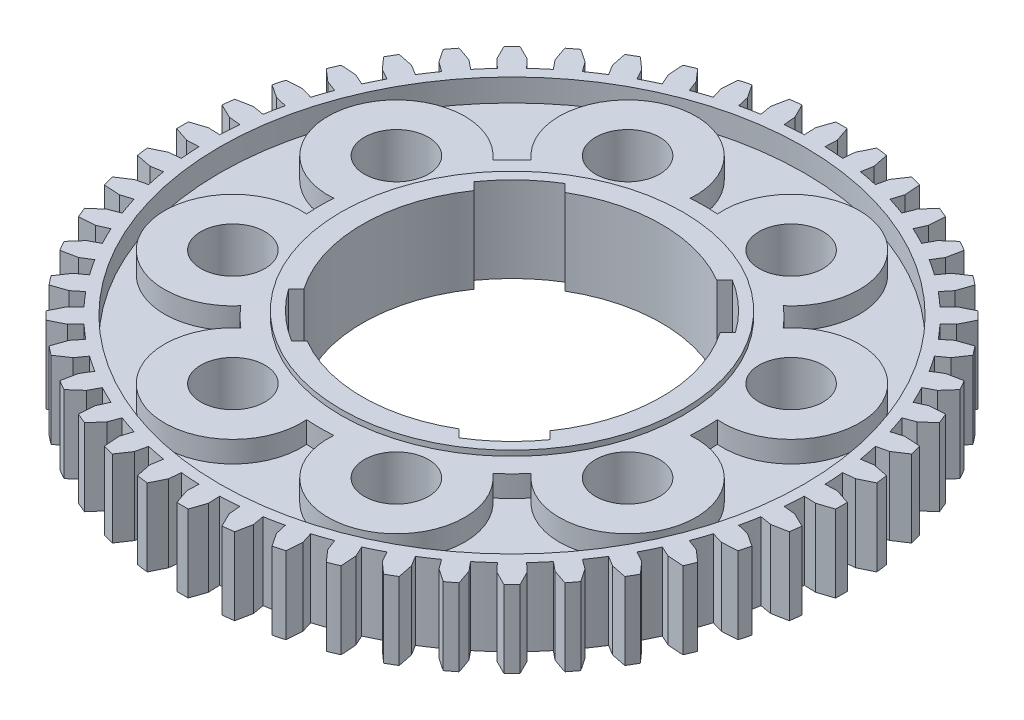
SolidWorks part; units mm, degrees
ref_plane "Plan de face" through (0, 0, 0) normal (0, 0, 1) x (1, 0, 0)
ref_plane "Plan de dessus" through (0, 0, 0) normal (0, 1, 0) x (1, 0, 0)
ref_plane "Plan de droite" through (0, 0, 0) normal (1, 0, 0) x (0, 0, -1)
sketch "Esquisse2" plane through (0, 0, 0) normal (0, 1, 0) x (1, 0, 0)
  line L0 (0, 15) -> (0, 0) construction
  line L1 (0, 0) -> (-15, 0) construction
  line L2 (0, 0) -> (-14, 0) construction
  line L3 (0, 0) -> (0, 14) construction
  line L4 (-7.8424, 12.7866) -> (-7.1138, 12.0579)
  line L5 (0, 0) -> (-15, 15) construction
  line L6 (-14, 0) -> (-18, 0) construction
  line L7 (-12.226, 8.6905) -> (-11.5081, 7.9726)
  line L8 (0, 15) -> (0, 18) construction
  line L9 (0, 0) -> (0, 27.6339) construction
  line L10 (0, 0) -> (-30.1339, 0) construction
  line L11 (0, 0) -> (-18.4776, 7.6537) construction
  line L12 (-27.8401, 11.5317) -> (0, 0) construction
  line L13 (0, 0) -> (-7.6537, 18.4776) construction
  line L14 (-7.6537, 18.4776) -> (-11.5317, 27.8401) construction
  line L15 (-27.8401, 11.5317) -> (-26.0855, 10.805) construction
  line L16 (-4.847, 29.0548) -> (-4.658, 27.9647)
  line L17 (0, 27.6339) -> (0, 30.1339) construction
  line L18 (-4.5538, 30.512) -> (-4.847, 29.0548)
  line L19 (-3.6069, 27.3975) -> (-3.9333, 29.8761) construction
  line L20 (-8.598, 28.1736) -> (-8.2683, 27.1175)
  line L21 (-8.4974, 29.6565) -> (-8.598, 28.1736)
  line L22 (-7.1522, 26.6923) -> (-7.7992, 29.1071) construction
  line L23 (-12.1907, 26.8151) -> (-11.7371, 25.8063)
  line L24 (-12.2957, 28.2937) -> (-12.1907, 26.8151)
  line L25 (0, 0) -> (-21.3079, 21.3079) construction
  line L26 (-10.575, 25.5304) -> (-11.5317, 27.8401) construction
  line L27 (-15.5865, 24.9945) -> (-15.0051, 24.0535)
  line L28 (-11.5317, 27.8401) -> (-10.805, 26.0855) construction
  line L29 (-15.8836, 26.4467) -> (-15.5865, 24.9945)
  line L30 (-13.8169, 23.9317) -> (-15.0669, 26.0967) construction
  line L31 (-18.7156, 22.7462) -> (-18.0163, 21.8892)
  line L32 (-19.1997, 24.1472) -> (-18.7156, 22.7462)
  line L33 (-16.8224, 21.9234) -> (-18.3444, 23.9068) construction
  line L34 (-21.5245, 20.1088) -> (-20.7193, 19.3503)
  line L35 (-22.1873, 21.4346) -> (-21.5245, 20.1088)
  line L36 (-19.5401, 19.5401) -> (-21.3079, 21.3079) construction
  line L37 (-23.965, 17.1272) -> (-23.0677, 16.4803)
  line L38 (-24.7952, 18.3552) -> (-23.965, 17.1272)
  line L39 (-21.9234, 16.8224) -> (-23.9068, 18.3444) construction
  line L40 (-25.9956, 13.8526) -> (-25.0215, 13.3284)
  line L41 (-26.9789, 14.9617) -> (-25.9956, 13.8526)
  line L42 (-23.9317, 13.8169) -> (-26.0967, 15.0669) construction
  line L43 (-27.5813, 10.341) -> (-26.5472, 9.9484)
  line L44 (-28.701, 11.3123) -> (-27.5813, 10.341)
  line L45 (-25.5304, 10.575) -> (-27.8401, 11.5317) construction
  line L46 (-28.6951, 6.6525) -> (-27.6186, 6.3982)
  line L47 (-29.932, 7.4693) -> (-28.6951, 6.6525)
  line L48 (-26.6923, 7.1522) -> (-29.1071, 7.7992) construction
  line L49 (-29.318, 2.8501) -> (-28.2174, 2.7385)
  line L50 (-30.6509, 3.4985) -> (-29.318, 2.8501)
  line L51 (-27.3975, 3.6069) -> (-29.8761, 3.9333) construction
  line L52 (-1.0131, 29.4389) -> (-1.0715, 30.8691) construction
  line L53 (-1.0131, -29.4389) -> (-1.0715, -30.8691) construction
  line L54 (-0.5322, 30.8453) -> (-1.0131, 29.4389)
  line L55 (-1.0131, 29.4389) -> (-0.968, 28.3335)
  line L56 (-27.3975, -3.6069) -> (-29.8761, -3.9333) construction
  line L57 (-27.6339, 0) -> (-30.1339, 0) construction
  line L58 (-3.4985, 30.6509) -> (-2.8381, 29.3193)
  line L59 (-2.8381, 29.3193) -> (-2.7385, 28.2174)
  line L60 (-7.4693, 29.932) -> (-6.6407, 28.698)
  line L61 (-6.6407, 28.698) -> (-6.3982, 27.6186)
  line L62 (-10.341, 27.5813) -> (-9.9484, 26.5472)
  line L63 (-11.3123, 28.701) -> (-10.341, 27.5813)
  line L64 (-14.9617, 26.9789) -> (-13.8526, 25.9956)
  line L65 (-13.8526, 25.9956) -> (-13.3284, 25.0215)
  line L66 (-18.3552, 24.7952) -> (-17.1272, 23.965)
  line L67 (-17.1272, 23.965) -> (-16.4803, 23.0677)
  line L68 (-30.512, 4.5538) -> (-29.0566, 4.8351)
  line L69 (-29.0566, 4.8351) -> (-27.9647, 4.658)
  line L70 (-29.6565, 8.4974) -> (-28.1769, 8.5864)
  line L71 (-28.1769, 8.5864) -> (-27.1175, 8.2683)
  line L72 (-28.2937, 12.2957) -> (-26.8151, 12.1907)
  line L73 (-26.8151, 12.1907) -> (-25.8063, 11.7371)
  line L74 (-26.4467, 15.8836) -> (-24.9945, 15.5865)
  line L75 (-24.9945, 15.5865) -> (-24.0535, 15.0051)
  line L76 (-24.1472, 19.1997) -> (-22.7462, 18.7156)
  line L77 (-22.7462, 18.7156) -> (-21.8892, 18.0163)
  line L78 (-21.4346, 22.1873) -> (-20.1088, 21.5245)
  line L79 (-20.1088, 21.5245) -> (-19.3503, 20.7193)
  line L80 (-30.8451, 0.5443) -> (-29.4389, 1.0131)
  line L81 (-29.4389, 1.0131) -> (-28.3335, 0.968)
  line L82 (-26.6923, -7.1522) -> (-29.1071, -7.7992) construction
  line L83 (-25.5304, -10.575) -> (-27.8401, -11.5317) construction
  line L84 (-23.9317, -13.8169) -> (-26.0967, -15.0669) construction
  line L85 (-21.9234, -16.8224) -> (-23.9068, -18.3444) construction
  line L86 (-19.5401, -19.5401) -> (-21.3079, -21.3079) construction
  line L87 (-16.8224, -21.9234) -> (-18.3444, -23.9068) construction
  line L88 (-13.8169, -23.9317) -> (-15.0669, -26.0967) construction
  line L89 (-11.5317, -27.8401) -> (-10.805, -26.0855) construction
  line L90 (-10.575, -25.5304) -> (-11.5317, -27.8401) construction
  line L91 (0, 0) -> (-21.3079, -21.3079) construction
  line L92 (-7.1522, -26.6923) -> (-7.7992, -29.1071) construction
  line L93 (-3.6069, -27.3975) -> (-3.9333, -29.8761) construction
  line L94 (0, -27.6339) -> (0, -30.1339) construction
  line L95 (-27.8401, -11.5317) -> (-26.0855, -10.805) construction
  line L96 (-7.6537, -18.4776) -> (-11.5317, -27.8401) construction
  line L97 (0, 0) -> (-7.6537, -18.4776) construction
  line L98 (-27.8401, -11.5317) -> (0, 0) construction
  line L99 (0, 0) -> (-18.4776, -7.6537) construction
  line L100 (0, 0) -> (0, -27.6339) construction
  line L101 (0, -15) -> (0, -18) construction
  line L102 (0, 0) -> (-15, -15) construction
  line L103 (0, 0) -> (0, -14) construction
  line L104 (0, -15) -> (0, 0) construction
  line L105 (-29.4389, -1.0131) -> (-28.3335, -0.968)
  line L106 (-30.8451, -0.5443) -> (-29.4389, -1.0131)
  line L107 (-20.1088, -21.5245) -> (-19.3503, -20.7193)
  line L108 (-21.4346, -22.1873) -> (-20.1088, -21.5245)
  line L109 (-22.7462, -18.7156) -> (-21.8892, -18.0163)
  line L110 (-24.1472, -19.1997) -> (-22.7462, -18.7156)
  line L111 (-24.9945, -15.5865) -> (-24.0535, -15.0051)
  line L112 (-26.4467, -15.8836) -> (-24.9945, -15.5865)
  line L113 (-26.8151, -12.1907) -> (-25.8063, -11.7371)
  line L114 (-28.2937, -12.2957) -> (-26.8151, -12.1907)
  line L115 (-28.1769, -8.5864) -> (-27.1175, -8.2683)
  line L116 (-29.6565, -8.4974) -> (-28.1769, -8.5864)
  line L117 (-29.0566, -4.8351) -> (-27.9647, -4.658)
  line L118 (-30.512, -4.5538) -> (-29.0566, -4.8351)
  line L119 (-17.1272, -23.965) -> (-16.4803, -23.0677)
  line L120 (-18.3552, -24.7952) -> (-17.1272, -23.965)
  line L121 (-13.8526, -25.9956) -> (-13.3284, -25.0215)
  line L122 (-14.9617, -26.9789) -> (-13.8526, -25.9956)
  line L123 (-11.3123, -28.701) -> (-10.341, -27.5813)
  line L124 (-10.341, -27.5813) -> (-9.9484, -26.5472)
  line L125 (-6.6407, -28.698) -> (-6.3982, -27.6186)
  line L126 (-7.4693, -29.932) -> (-6.6407, -28.698)
  line L127 (-2.8381, -29.3193) -> (-2.7385, -28.2174)
  line L128 (-3.4985, -30.6509) -> (-2.8381, -29.3193)
  line L129 (-1.0131, -29.4389) -> (-0.968, -28.3335)
  line L130 (-0.5322, -30.8453) -> (-1.0131, -29.4389)
  line L131 (-30.6509, -3.4985) -> (-29.318, -2.8501)
  line L132 (-29.318, -2.8501) -> (-28.2174, -2.7385)
  line L133 (-29.932, -7.4693) -> (-28.6951, -6.6525)
  line L134 (-28.6951, -6.6525) -> (-27.6186, -6.3982)
  line L135 (-28.701, -11.3123) -> (-27.5813, -10.341)
  line L136 (-27.5813, -10.341) -> (-26.5472, -9.9484)
  line L137 (-26.9789, -14.9617) -> (-25.9956, -13.8526)
  line L138 (-25.9956, -13.8526) -> (-25.0215, -13.3284)
  line L139 (-24.7952, -18.3552) -> (-23.965, -17.1272)
  line L140 (-23.965, -17.1272) -> (-23.0677, -16.4803)
  line L141 (-22.1873, -21.4346) -> (-21.5245, -20.1088)
  line L142 (-21.5245, -20.1088) -> (-20.7193, -19.3503)
  line L143 (-19.1997, -24.1472) -> (-18.7156, -22.7462)
  line L144 (-18.7156, -22.7462) -> (-18.0163, -21.8892)
  line L145 (-15.8836, -26.4467) -> (-15.5865, -24.9945)
  line L146 (-15.5865, -24.9945) -> (-15.0051, -24.0535)
  line L147 (-12.2957, -28.2937) -> (-12.1907, -26.8151)
  line L148 (-12.1907, -26.8151) -> (-11.7371, -25.8063)
  line L149 (-8.4974, -29.6565) -> (-8.598, -28.1736)
  line L150 (-8.598, -28.1736) -> (-8.2683, -27.1175)
  line L151 (-4.5538, -30.512) -> (-4.847, -29.0548)
  line L152 (-4.847, -29.0548) -> (-4.658, -27.9647)
  line L153 (-12.226, -8.6905) -> (-11.5081, -7.9726)
  line L154 (-7.8424, -12.7866) -> (-7.1138, -12.0579)
  line L155 (0, 0) -> (15, -15) construction
  line L156 (0, 0) -> (18.4776, -7.6537) construction
  line L157 (27.8401, -11.5317) -> (0, 0) construction
  line L158 (0, 0) -> (7.6537, -18.4776) construction
  line L159 (7.6537, -18.4776) -> (11.5317, -27.8401) construction
  line L160 (27.8401, -11.5317) -> (26.0855, -10.805) construction
  line L161 (3.6069, -27.3975) -> (3.9333, -29.8761) construction
  line L162 (7.1522, -26.6923) -> (7.7992, -29.1071) construction
  line L163 (0, 0) -> (21.3079, -21.3079) construction
  line L164 (10.575, -25.5304) -> (11.5317, -27.8401) construction
  line L165 (11.5317, -27.8401) -> (10.805, -26.0855) construction
  line L166 (13.8169, -23.9317) -> (15.0669, -26.0967) construction
  line L167 (16.8224, -21.9234) -> (18.3444, -23.9068) construction
  line L168 (19.5401, -19.5401) -> (21.3079, -21.3079) construction
  line L169 (21.9234, -16.8224) -> (23.9068, -18.3444) construction
  line L170 (23.9317, -13.8169) -> (26.0967, -15.0669) construction
  line L171 (25.5304, -10.575) -> (27.8401, -11.5317) construction
  line L172 (26.6923, -7.1522) -> (29.1071, -7.7992) construction
  line L173 (27.6339, 0) -> (30.1339, 0) construction
  line L174 (27.3975, -3.6069) -> (29.8761, -3.9333) construction
  line L175 (1.0131, -29.4389) -> (1.0715, -30.8691) construction
  line L176 (1.0131, 29.4389) -> (1.0715, 30.8691) construction
  line L177 (27.3975, 3.6069) -> (29.8761, 3.9333) construction
  line L178 (26.6923, 7.1522) -> (29.1071, 7.7992) construction
  line L179 (25.5304, 10.575) -> (27.8401, 11.5317) construction
  line L180 (23.9317, 13.8169) -> (26.0967, 15.0669) construction
  line L181 (21.9234, 16.8224) -> (23.9068, 18.3444) construction
  line L182 (19.5401, 19.5401) -> (21.3079, 21.3079) construction
  line L183 (16.8224, 21.9234) -> (18.3444, 23.9068) construction
  line L184 (13.8169, 23.9317) -> (15.0669, 26.0967) construction
  line L185 (11.5317, 27.8401) -> (10.805, 26.0855) construction
  line L186 (10.575, 25.5304) -> (11.5317, 27.8401) construction
  line L187 (0, 0) -> (21.3079, 21.3079) construction
  line L188 (7.1522, 26.6923) -> (7.7992, 29.1071) construction
  line L189 (3.6069, 27.3975) -> (3.9333, 29.8761) construction
  line L190 (27.8401, 11.5317) -> (26.0855, 10.805) construction
  line L191 (7.6537, 18.4776) -> (11.5317, 27.8401) construction
  line L192 (0, 0) -> (7.6537, 18.4776) construction
  line L193 (27.8401, 11.5317) -> (0, 0) construction
  line L194 (0, 0) -> (18.4776, 7.6537) construction
  line L195 (0, 0) -> (30.1339, 0) construction
  line L196 (14, 0) -> (18, 0) construction
  line L197 (0, 0) -> (15, 15) construction
  line L198 (0, 0) -> (14, 0) construction
  line L199 (0, 0) -> (15, 0) construction
  line L200 (7.8424, -12.7866) -> (7.1138, -12.0579)
  line L201 (12.226, -8.6905) -> (11.5081, -7.9726)
  line L202 (4.847, -29.0548) -> (4.658, -27.9647)
  line L203 (4.5538, -30.512) -> (4.847, -29.0548)
  line L204 (8.598, -28.1736) -> (8.2683, -27.1175)
  line L205 (8.4974, -29.6565) -> (8.598, -28.1736)
  line L206 (12.1907, -26.8151) -> (11.7371, -25.8063)
  line L207 (12.2957, -28.2937) -> (12.1907, -26.8151)
  line L208 (15.5865, -24.9945) -> (15.0051, -24.0535)
  line L209 (15.8836, -26.4467) -> (15.5865, -24.9945)
  line L210 (18.7156, -22.7462) -> (18.0163, -21.8892)
  line L211 (19.1997, -24.1472) -> (18.7156, -22.7462)
  line L212 (21.5245, -20.1088) -> (20.7193, -19.3503)
  line L213 (22.1873, -21.4346) -> (21.5245, -20.1088)
  line L214 (23.965, -17.1272) -> (23.0677, -16.4803)
  line L215 (24.7952, -18.3552) -> (23.965, -17.1272)
  line L216 (25.9956, -13.8526) -> (25.0215, -13.3284)
  line L217 (26.9789, -14.9617) -> (25.9956, -13.8526)
  line L218 (27.5813, -10.341) -> (26.5472, -9.9484)
  line L219 (28.701, -11.3123) -> (27.5813, -10.341)
  line L220 (28.6951, -6.6525) -> (27.6186, -6.3982)
  line L221 (29.932, -7.4693) -> (28.6951, -6.6525)
  line L222 (29.318, -2.8501) -> (28.2174, -2.7385)
  line L223 (30.6509, -3.4985) -> (29.318, -2.8501)
  line L224 (0.5322, -30.8453) -> (1.0131, -29.4389)
  line L225 (1.0131, -29.4389) -> (0.968, -28.3335)
  line L226 (3.4985, -30.6509) -> (2.8381, -29.3193)
  line L227 (2.8381, -29.3193) -> (2.7385, -28.2174)
  line L228 (7.4693, -29.932) -> (6.6407, -28.698)
  line L229 (6.6407, -28.698) -> (6.3982, -27.6186)
  line L230 (10.341, -27.5813) -> (9.9484, -26.5472)
  line L231 (11.3123, -28.701) -> (10.341, -27.5813)
  line L232 (14.9617, -26.9789) -> (13.8526, -25.9956)
  line L233 (13.8526, -25.9956) -> (13.3284, -25.0215)
  line L234 (18.3552, -24.7952) -> (17.1272, -23.965)
  line L235 (17.1272, -23.965) -> (16.4803, -23.0677)
  line L236 (30.512, -4.5538) -> (29.0566, -4.8351)
  line L237 (29.0566, -4.8351) -> (27.9647, -4.658)
  line L238 (29.6565, -8.4974) -> (28.1769, -8.5864)
  line L239 (28.1769, -8.5864) -> (27.1175, -8.2683)
  line L240 (28.2937, -12.2957) -> (26.8151, -12.1907)
  line L241 (26.8151, -12.1907) -> (25.8063, -11.7371)
  line L242 (26.4467, -15.8836) -> (24.9945, -15.5865)
  line L243 (24.9945, -15.5865) -> (24.0535, -15.0051)
  line L244 (24.1472, -19.1997) -> (22.7462, -18.7156)
  line L245 (22.7462, -18.7156) -> (21.8892, -18.0163)
  line L246 (21.4346, -22.1873) -> (20.1088, -21.5245)
  line L247 (20.1088, -21.5245) -> (19.3503, -20.7193)
  line L248 (30.8451, -0.5443) -> (29.4389, -1.0131)
  line L249 (29.4389, -1.0131) -> (28.3335, -0.968)
  line L250 (29.4389, 1.0131) -> (28.3335, 0.968)
  line L251 (30.8451, 0.5443) -> (29.4389, 1.0131)
  line L252 (20.1088, 21.5245) -> (19.3503, 20.7193)
  line L253 (21.4346, 22.1873) -> (20.1088, 21.5245)
  line L254 (22.7462, 18.7156) -> (21.8892, 18.0163)
  line L255 (24.1472, 19.1997) -> (22.7462, 18.7156)
  line L256 (24.9945, 15.5865) -> (24.0535, 15.0051)
  line L257 (26.4467, 15.8836) -> (24.9945, 15.5865)
  line L258 (26.8151, 12.1907) -> (25.8063, 11.7371)
  line L259 (28.2937, 12.2957) -> (26.8151, 12.1907)
  line L260 (28.1769, 8.5864) -> (27.1175, 8.2683)
  line L261 (29.6565, 8.4974) -> (28.1769, 8.5864)
  line L262 (29.0566, 4.8351) -> (27.9647, 4.658)
  line L263 (30.512, 4.5538) -> (29.0566, 4.8351)
  line L264 (17.1272, 23.965) -> (16.4803, 23.0677)
  line L265 (18.3552, 24.7952) -> (17.1272, 23.965)
  line L266 (13.8526, 25.9956) -> (13.3284, 25.0215)
  line L267 (14.9617, 26.9789) -> (13.8526, 25.9956)
  line L268 (11.3123, 28.701) -> (10.341, 27.5813)
  line L269 (10.341, 27.5813) -> (9.9484, 26.5472)
  line L270 (6.6407, 28.698) -> (6.3982, 27.6186)
  line L271 (7.4693, 29.932) -> (6.6407, 28.698)
  line L272 (2.8381, 29.3193) -> (2.7385, 28.2174)
  line L273 (3.4985, 30.6509) -> (2.8381, 29.3193)
  line L274 (1.0131, 29.4389) -> (0.968, 28.3335)
  line L275 (0.5322, 30.8453) -> (1.0131, 29.4389)
  line L276 (30.6509, 3.4985) -> (29.318, 2.8501)
  line L277 (29.318, 2.8501) -> (28.2174, 2.7385)
  line L278 (29.932, 7.4693) -> (28.6951, 6.6525)
  line L279 (28.6951, 6.6525) -> (27.6186, 6.3982)
  line L280 (28.701, 11.3123) -> (27.5813, 10.341)
  line L281 (27.5813, 10.341) -> (26.5472, 9.9484)
  line L282 (26.9789, 14.9617) -> (25.9956, 13.8526)
  line L283 (25.9956, 13.8526) -> (25.0215, 13.3284)
  line L284 (24.7952, 18.3552) -> (23.965, 17.1272)
  line L285 (23.965, 17.1272) -> (23.0677, 16.4803)
  line L286 (22.1873, 21.4346) -> (21.5245, 20.1088)
  line L287 (21.5245, 20.1088) -> (20.7193, 19.3503)
  line L288 (19.1997, 24.1472) -> (18.7156, 22.7462)
  line L289 (18.7156, 22.7462) -> (18.0163, 21.8892)
  line L290 (15.8836, 26.4467) -> (15.5865, 24.9945)
  line L291 (15.5865, 24.9945) -> (15.0051, 24.0535)
  line L292 (12.2957, 28.2937) -> (12.1907, 26.8151)
  line L293 (12.1907, 26.8151) -> (11.7371, 25.8063)
  line L294 (8.4974, 29.6565) -> (8.598, 28.1736)
  line L295 (8.598, 28.1736) -> (8.2683, 27.1175)
  line L296 (4.5538, 30.512) -> (4.847, 29.0548)
  line L297 (4.847, 29.0548) -> (4.658, 27.9647)
  line L298 (12.226, 8.6905) -> (11.5081, 7.9726)
  line L299 (7.8424, 12.7866) -> (7.1138, 12.0579)
  arc A0 (-7.8424, 12.7866) -> (-12.226, 8.6905) centre (0, 0) ccw
  arc A1 (7.1138, 12.0579) -> (-7.1138, 12.0579) centre (0, 0) ccw
  arc A2 (-11.5081, 7.9726) -> (-11.5081, -7.9726) centre (0, 0) ccw
  arc A3 (-17.9548, 1.2751) -> (-17.9548, -1.2751) centre (0, 0) ccw
  circle A4 centre (-7.6537, 18.4776) radius 3
  arc A5 (-1.2751, 17.9548) -> (-11.7943, 13.5976) centre (-7.6537, 18.4776) ccw
  arc A6 (-17.9548, 1.2751) -> (-13.5976, 11.7943) centre (-18.4776, 7.6537) cw
  circle A7 centre (-18.4776, 7.6537) radius 3
  arc A8 (-11.7943, 13.5976) -> (-13.5976, 11.7943) centre (0, 0) ccw
  arc A9 (1.2751, 17.9548) -> (-1.2751, 17.9548) centre (0, 0) ccw
  circle A10 centre (0, 0) radius 27.35
  circle A11 centre (0, 0) radius 16
  arc A12 (-0.968, 28.3335) -> (-2.7385, 28.2174) centre (0, 0) ccw
  arc A14 (0.5322, 30.8453) -> (-0.5322, 30.8453) centre (0, 0) ccw
  arc A15 (-30.8451, 0.5443) -> (-30.8451, -0.5443) centre (0, 0) ccw
  arc A16 (-26.5472, 9.9484) -> (-27.1175, 8.2683) centre (0, 0) ccw
  arc A19 (-30.512, 4.5538) -> (-30.6509, 3.4985) centre (0, 0) ccw
  arc A20 (-11.7371, 25.8063) -> (-13.3284, 25.0215) centre (0, 0) ccw
  arc A21 (-29.6565, 8.4974) -> (-29.932, 7.4693) centre (0, 0) ccw
  arc A22 (-28.2937, 12.2957) -> (-28.701, 11.3123) centre (0, 0) ccw
  arc A23 (-26.4467, 15.8836) -> (-26.9789, 14.9617) centre (0, 0) ccw
  arc A24 (-24.1472, 19.1997) -> (-24.7952, 18.3552) centre (0, 0) ccw
  arc A25 (-21.4346, 22.1873) -> (-22.1873, 21.4346) centre (0, 0) ccw
  arc A27 (-18.3552, 24.7952) -> (-19.1997, 24.1472) centre (0, 0) ccw
  arc A28 (-14.9617, 26.9789) -> (-15.8836, 26.4467) centre (0, 0) ccw
  arc A29 (-11.3123, 28.701) -> (-12.2957, 28.2937) centre (0, 0) ccw
  arc A32 (-7.4693, 29.932) -> (-8.4974, 29.6565) centre (0, 0) ccw
  arc A33 (-3.4985, 30.6509) -> (-4.5538, 30.512) centre (0, 0) ccw
  arc A34 (-4.658, 27.9647) -> (-6.3982, 27.6186) centre (0, 0) ccw
  arc A35 (-8.2683, 27.1175) -> (-9.9484, 26.5472) centre (0, 0) ccw
  arc A44 (-11.7371, 25.8063) -> (-13.3284, 25.0215) centre (0, 0) ccw
  arc A59 (-15.0051, 24.0535) -> (-16.4803, 23.0677) centre (0, 0) ccw
  arc A60 (-18.0163, 21.8892) -> (-19.3503, 20.7193) centre (0, 0) ccw
  arc A61 (-20.7193, 19.3503) -> (-21.8892, 18.0163) centre (0, 0) ccw
  arc A62 (-23.0677, 16.4803) -> (-24.0535, 15.0051) centre (0, 0) ccw
  arc A63 (-25.0215, 13.3284) -> (-25.8063, 11.7371) centre (0, 0) ccw
  arc A64 (-26.5472, 9.9484) -> (-27.1175, 8.2683) centre (0, 0) ccw
  arc A65 (-27.6186, 6.3982) -> (-27.9647, 4.658) centre (0, 0) ccw
  arc A66 (-28.2174, 2.7385) -> (-28.3335, 0.968) centre (0, 0) ccw
  arc A67 (-0.968, 28.3335) -> (-2.7385, 28.2174) centre (0, 0) ccw
  arc A68 (-0.968, 28.3335) -> (-2.7385, 28.2174) centre (0, 0) ccw
  arc A69 (-28.2174, 2.7385) -> (-28.3335, 0.968) centre (0, 0) ccw
  arc A70 (-27.6186, 6.3982) -> (-27.9647, 4.658) centre (0, 0) ccw
  arc A71 (-27.6186, 6.3982) -> (-28.3335, 0.968) centre (0, 0) ccw
  arc A72 (-26.5472, 9.9484) -> (-27.1175, 8.2683) centre (0, 0) ccw
  arc A73 (-25.0215, 13.3284) -> (-25.8063, 11.7371) centre (0, 0) ccw
  arc A74 (-25.0215, 13.3284) -> (-25.8063, 11.7371) centre (0, 0) ccw
  arc A75 (-23.0677, 16.4803) -> (-24.0535, 15.0051) centre (0, 0) ccw
  arc A76 (-23.0677, 16.4803) -> (-24.0535, 15.0051) centre (0, 0) ccw
  arc A77 (-20.7193, 19.3503) -> (-21.8892, 18.0163) centre (0, 0) ccw
  arc A78 (-20.7193, 19.3503) -> (-21.8892, 18.0163) centre (0, 0) ccw
  arc A79 (-18.0163, 21.8892) -> (-19.3503, 20.7193) centre (0, 0) ccw
  arc A80 (-18.0163, 21.8892) -> (-19.3503, 20.7193) centre (0, 0) ccw
  arc A81 (-15.0051, 24.0535) -> (-16.4803, 23.0677) centre (0, 0) ccw
  arc A82 (-15.0051, 24.0535) -> (-16.4803, 23.0677) centre (0, 0) ccw
  arc A83 (-11.7371, 25.8063) -> (-13.3284, 25.0215) centre (0, 0) ccw
  arc A84 (-8.2683, 27.1175) -> (-9.9484, 26.5472) centre (0, 0) ccw
  arc A85 (-8.2683, 27.1175) -> (-9.9484, 26.5472) centre (0, 0) ccw
  arc A86 (-4.658, 27.9647) -> (-6.3982, 27.6186) centre (0, 0) ccw
  arc A87 (-4.658, 27.9647) -> (-6.3982, 27.6186) centre (0, 0) ccw
  arc A88 (-4.658, -27.9647) -> (-6.3982, -27.6186) centre (0, 0) cw
  arc A89 (-4.658, -27.9647) -> (-6.3982, -27.6186) centre (0, 0) cw
  arc A90 (-8.2683, -27.1175) -> (-9.9484, -26.5472) centre (0, 0) cw
  arc A91 (-8.2683, -27.1175) -> (-9.9484, -26.5472) centre (0, 0) cw
  arc A92 (-11.7371, -25.8063) -> (-13.3284, -25.0215) centre (0, 0) cw
  arc A93 (-15.0051, -24.0535) -> (-16.4803, -23.0677) centre (0, 0) cw
  arc A94 (-15.0051, -24.0535) -> (-16.4803, -23.0677) centre (0, 0) cw
  arc A95 (-18.0163, -21.8892) -> (-19.3503, -20.7193) centre (0, 0) cw
  arc A96 (-18.0163, -21.8892) -> (-19.3503, -20.7193) centre (0, 0) cw
  arc A97 (-20.7193, -19.3503) -> (-21.8892, -18.0163) centre (0, 0) cw
  arc A98 (-20.7193, -19.3503) -> (-21.8892, -18.0163) centre (0, 0) cw
  arc A99 (-23.0677, -16.4803) -> (-24.0535, -15.0051) centre (0, 0) cw
  arc A100 (-23.0677, -16.4803) -> (-24.0535, -15.0051) centre (0, 0) cw
  arc A101 (-25.0215, -13.3284) -> (-25.8063, -11.7371) centre (0, 0) cw
  arc A102 (-25.0215, -13.3284) -> (-25.8063, -11.7371) centre (0, 0) cw
  arc A103 (-26.5472, -9.9484) -> (-27.1175, -8.2683) centre (0, 0) cw
  arc A104 (-27.6186, -6.3982) -> (-28.3335, -0.968) centre (0, 0) cw
  arc A105 (-27.6186, -6.3982) -> (-27.9647, -4.658) centre (0, 0) cw
  arc A106 (-28.2174, -2.7385) -> (-28.3335, -0.968) centre (0, 0) cw
  arc A107 (-0.968, -28.3335) -> (-2.7385, -28.2174) centre (0, 0) cw
  arc A108 (-0.968, -28.3335) -> (-2.7385, -28.2174) centre (0, 0) cw
  arc A109 (-28.2174, -2.7385) -> (-28.3335, -0.968) centre (0, 0) cw
  arc A110 (-27.6186, -6.3982) -> (-27.9647, -4.658) centre (0, 0) cw
  arc A111 (-26.5472, -9.9484) -> (-27.1175, -8.2683) centre (0, 0) cw
  arc A112 (-25.0215, -13.3284) -> (-25.8063, -11.7371) centre (0, 0) cw
  arc A113 (-23.0677, -16.4803) -> (-24.0535, -15.0051) centre (0, 0) cw
  arc A114 (-20.7193, -19.3503) -> (-21.8892, -18.0163) centre (0, 0) cw
  arc A115 (-18.0163, -21.8892) -> (-19.3503, -20.7193) centre (0, 0) cw
  arc A116 (-15.0051, -24.0535) -> (-16.4803, -23.0677) centre (0, 0) cw
  arc A117 (-11.7371, -25.8063) -> (-13.3284, -25.0215) centre (0, 0) cw
  arc A118 (-8.2683, -27.1175) -> (-9.9484, -26.5472) centre (0, 0) cw
  arc A119 (-4.658, -27.9647) -> (-6.3982, -27.6186) centre (0, 0) cw
  arc A120 (-3.4985, -30.6509) -> (-4.5538, -30.512) centre (0, 0) cw
  arc A121 (-7.4693, -29.932) -> (-8.4974, -29.6565) centre (0, 0) cw
  arc A122 (-11.3123, -28.701) -> (-12.2957, -28.2937) centre (0, 0) cw
  arc A123 (-14.9617, -26.9789) -> (-15.8836, -26.4467) centre (0, 0) cw
  arc A124 (-18.3552, -24.7952) -> (-19.1997, -24.1472) centre (0, 0) cw
  arc A125 (-21.4346, -22.1873) -> (-22.1873, -21.4346) centre (0, 0) cw
  arc A126 (-24.1472, -19.1997) -> (-24.7952, -18.3552) centre (0, 0) cw
  arc A127 (-26.4467, -15.8836) -> (-26.9789, -14.9617) centre (0, 0) cw
  arc A128 (-28.2937, -12.2957) -> (-28.701, -11.3123) centre (0, 0) cw
  arc A129 (-29.6565, -8.4974) -> (-29.932, -7.4693) centre (0, 0) cw
  arc A130 (-11.7371, -25.8063) -> (-13.3284, -25.0215) centre (0, 0) cw
  arc A131 (-30.512, -4.5538) -> (-30.6509, -3.4985) centre (0, 0) cw
  arc A132 (-26.5472, -9.9484) -> (-27.1175, -8.2683) centre (0, 0) cw
  arc A133 (0.5322, -30.8453) -> (-0.5322, -30.8453) centre (0, 0) cw
  arc A134 (-0.968, -28.3335) -> (-2.7385, -28.2174) centre (0, 0) cw
  arc A135 (1.2751, -17.9548) -> (-1.2751, -17.9548) centre (0, 0) cw
  arc A136 (-11.7943, -13.5976) -> (-13.5976, -11.7943) centre (0, 0) cw
  circle A137 centre (-18.4776, -7.6537) radius 3
  arc A138 (-17.9548, -1.2751) -> (-13.5976, -11.7943) centre (-18.4776, -7.6537) ccw
  arc A139 (-1.2751, -17.9548) -> (-11.7943, -13.5976) centre (-7.6537, -18.4776) cw
  circle A140 centre (-7.6537, -18.4776) radius 3
  arc A141 (7.1138, -12.0579) -> (-7.1138, -12.0579) centre (0, 0) cw
  arc A142 (-7.8424, -12.7866) -> (-12.226, -8.6905) centre (0, 0) cw
  arc A143 (7.8424, -12.7866) -> (12.226, -8.6905) centre (0, 0) ccw
  circle A144 centre (7.6537, -18.4776) radius 3
  arc A145 (1.2751, -17.9548) -> (11.7943, -13.5976) centre (7.6537, -18.4776) ccw
  arc A146 (17.9548, -1.2751) -> (13.5976, -11.7943) centre (18.4776, -7.6537) cw
  circle A147 centre (18.4776, -7.6537) radius 3
  arc A148 (11.7943, -13.5976) -> (13.5976, -11.7943) centre (0, 0) ccw
  arc A149 (0.968, -28.3335) -> (2.7385, -28.2174) centre (0, 0) ccw
  arc A150 (26.5472, -9.9484) -> (27.1175, -8.2683) centre (0, 0) ccw
  arc A151 (30.512, -4.5538) -> (30.6509, -3.4985) centre (0, 0) ccw
  arc A152 (11.7371, -25.8063) -> (13.3284, -25.0215) centre (0, 0) ccw
  arc A153 (29.6565, -8.4974) -> (29.932, -7.4693) centre (0, 0) ccw
  arc A154 (28.2937, -12.2957) -> (28.701, -11.3123) centre (0, 0) ccw
  arc A155 (26.4467, -15.8836) -> (26.9789, -14.9617) centre (0, 0) ccw
  arc A156 (24.1472, -19.1997) -> (24.7952, -18.3552) centre (0, 0) ccw
  arc A157 (21.4346, -22.1873) -> (22.1873, -21.4346) centre (0, 0) ccw
  arc A158 (18.3552, -24.7952) -> (19.1997, -24.1472) centre (0, 0) ccw
  arc A159 (14.9617, -26.9789) -> (15.8836, -26.4467) centre (0, 0) ccw
  arc A160 (11.3123, -28.701) -> (12.2957, -28.2937) centre (0, 0) ccw
  arc A161 (7.4693, -29.932) -> (8.4974, -29.6565) centre (0, 0) ccw
  arc A162 (3.4985, -30.6509) -> (4.5538, -30.512) centre (0, 0) ccw
  arc A163 (4.658, -27.9647) -> (6.3982, -27.6186) centre (0, 0) ccw
  arc A164 (8.2683, -27.1175) -> (9.9484, -26.5472) centre (0, 0) ccw
  arc A165 (11.7371, -25.8063) -> (13.3284, -25.0215) centre (0, 0) ccw
  arc A166 (15.0051, -24.0535) -> (16.4803, -23.0677) centre (0, 0) ccw
  arc A167 (18.0163, -21.8892) -> (19.3503, -20.7193) centre (0, 0) ccw
  arc A168 (20.7193, -19.3503) -> (21.8892, -18.0163) centre (0, 0) ccw
  arc A169 (23.0677, -16.4803) -> (24.0535, -15.0051) centre (0, 0) ccw
  arc A170 (25.0215, -13.3284) -> (25.8063, -11.7371) centre (0, 0) ccw
  arc A171 (26.5472, -9.9484) -> (27.1175, -8.2683) centre (0, 0) ccw
  arc A172 (27.6186, -6.3982) -> (27.9647, -4.658) centre (0, 0) ccw
  arc A173 (28.2174, -2.7385) -> (28.3335, -0.968) centre (0, 0) ccw
  arc A174 (0.968, -28.3335) -> (2.7385, -28.2174) centre (0, 0) ccw
  arc A175 (0.968, -28.3335) -> (2.7385, -28.2174) centre (0, 0) ccw
  arc A176 (28.2174, -2.7385) -> (28.3335, -0.968) centre (0, 0) ccw
  arc A177 (27.6186, -6.3982) -> (27.9647, -4.658) centre (0, 0) ccw
  arc A178 (27.6186, -6.3982) -> (28.3335, -0.968) centre (0, 0) ccw
  arc A179 (26.5472, -9.9484) -> (27.1175, -8.2683) centre (0, 0) ccw
  arc A180 (25.0215, -13.3284) -> (25.8063, -11.7371) centre (0, 0) ccw
  arc A181 (25.0215, -13.3284) -> (25.8063, -11.7371) centre (0, 0) ccw
  arc A182 (23.0677, -16.4803) -> (24.0535, -15.0051) centre (0, 0) ccw
  arc A183 (23.0677, -16.4803) -> (24.0535, -15.0051) centre (0, 0) ccw
  arc A184 (20.7193, -19.3503) -> (21.8892, -18.0163) centre (0, 0) ccw
  arc A185 (20.7193, -19.3503) -> (21.8892, -18.0163) centre (0, 0) ccw
  arc A186 (18.0163, -21.8892) -> (19.3503, -20.7193) centre (0, 0) ccw
  arc A187 (18.0163, -21.8892) -> (19.3503, -20.7193) centre (0, 0) ccw
  arc A188 (15.0051, -24.0535) -> (16.4803, -23.0677) centre (0, 0) ccw
  arc A189 (15.0051, -24.0535) -> (16.4803, -23.0677) centre (0, 0) ccw
  arc A190 (11.7371, -25.8063) -> (13.3284, -25.0215) centre (0, 0) ccw
  arc A191 (8.2683, -27.1175) -> (9.9484, -26.5472) centre (0, 0) ccw
  arc A192 (8.2683, -27.1175) -> (9.9484, -26.5472) centre (0, 0) ccw
  arc A193 (4.658, -27.9647) -> (6.3982, -27.6186) centre (0, 0) ccw
  arc A194 (4.658, -27.9647) -> (6.3982, -27.6186) centre (0, 0) ccw
  arc A195 (4.658, 27.9647) -> (6.3982, 27.6186) centre (0, 0) cw
  arc A196 (4.658, 27.9647) -> (6.3982, 27.6186) centre (0, 0) cw
  arc A197 (8.2683, 27.1175) -> (9.9484, 26.5472) centre (0, 0) cw
  arc A198 (8.2683, 27.1175) -> (9.9484, 26.5472) centre (0, 0) cw
  arc A199 (11.7371, 25.8063) -> (13.3284, 25.0215) centre (0, 0) cw
  arc A200 (15.0051, 24.0535) -> (16.4803, 23.0677) centre (0, 0) cw
  arc A201 (15.0051, 24.0535) -> (16.4803, 23.0677) centre (0, 0) cw
  arc A202 (18.0163, 21.8892) -> (19.3503, 20.7193) centre (0, 0) cw
  arc A203 (18.0163, 21.8892) -> (19.3503, 20.7193) centre (0, 0) cw
  arc A204 (20.7193, 19.3503) -> (21.8892, 18.0163) centre (0, 0) cw
  arc A205 (20.7193, 19.3503) -> (21.8892, 18.0163) centre (0, 0) cw
  arc A206 (23.0677, 16.4803) -> (24.0535, 15.0051) centre (0, 0) cw
  arc A207 (23.0677, 16.4803) -> (24.0535, 15.0051) centre (0, 0) cw
  arc A208 (25.0215, 13.3284) -> (25.8063, 11.7371) centre (0, 0) cw
  arc A209 (25.0215, 13.3284) -> (25.8063, 11.7371) centre (0, 0) cw
  arc A210 (26.5472, 9.9484) -> (27.1175, 8.2683) centre (0, 0) cw
  arc A211 (27.6186, 6.3982) -> (28.3335, 0.968) centre (0, 0) cw
  arc A212 (27.6186, 6.3982) -> (27.9647, 4.658) centre (0, 0) cw
  arc A213 (28.2174, 2.7385) -> (28.3335, 0.968) centre (0, 0) cw
  arc A214 (0.968, 28.3335) -> (2.7385, 28.2174) centre (0, 0) cw
  arc A215 (0.968, 28.3335) -> (2.7385, 28.2174) centre (0, 0) cw
  arc A216 (28.2174, 2.7385) -> (28.3335, 0.968) centre (0, 0) cw
  arc A217 (27.6186, 6.3982) -> (27.9647, 4.658) centre (0, 0) cw
  arc A218 (26.5472, 9.9484) -> (27.1175, 8.2683) centre (0, 0) cw
  arc A219 (25.0215, 13.3284) -> (25.8063, 11.7371) centre (0, 0) cw
  arc A220 (23.0677, 16.4803) -> (24.0535, 15.0051) centre (0, 0) cw
  arc A221 (20.7193, 19.3503) -> (21.8892, 18.0163) centre (0, 0) cw
  arc A222 (18.0163, 21.8892) -> (19.3503, 20.7193) centre (0, 0) cw
  arc A223 (15.0051, 24.0535) -> (16.4803, 23.0677) centre (0, 0) cw
  arc A224 (11.7371, 25.8063) -> (13.3284, 25.0215) centre (0, 0) cw
  arc A225 (8.2683, 27.1175) -> (9.9484, 26.5472) centre (0, 0) cw
  arc A226 (4.658, 27.9647) -> (6.3982, 27.6186) centre (0, 0) cw
  arc A227 (3.4985, 30.6509) -> (4.5538, 30.512) centre (0, 0) cw
  arc A228 (7.4693, 29.932) -> (8.4974, 29.6565) centre (0, 0) cw
  arc A229 (11.3123, 28.701) -> (12.2957, 28.2937) centre (0, 0) cw
  arc A230 (14.9617, 26.9789) -> (15.8836, 26.4467) centre (0, 0) cw
  arc A231 (18.3552, 24.7952) -> (19.1997, 24.1472) centre (0, 0) cw
  arc A232 (21.4346, 22.1873) -> (22.1873, 21.4346) centre (0, 0) cw
  arc A233 (24.1472, 19.1997) -> (24.7952, 18.3552) centre (0, 0) cw
  arc A234 (26.4467, 15.8836) -> (26.9789, 14.9617) centre (0, 0) cw
  arc A235 (28.2937, 12.2957) -> (28.701, 11.3123) centre (0, 0) cw
  arc A236 (29.6565, 8.4974) -> (29.932, 7.4693) centre (0, 0) cw
  arc A237 (11.7371, 25.8063) -> (13.3284, 25.0215) centre (0, 0) cw
  arc A238 (30.512, 4.5538) -> (30.6509, 3.4985) centre (0, 0) cw
  arc A239 (26.5472, 9.9484) -> (27.1175, 8.2683) centre (0, 0) cw
  arc A240 (30.8451, 0.5443) -> (30.8451, -0.5443) centre (0, 0) cw
  arc A241 (0.968, 28.3335) -> (2.7385, 28.2174) centre (0, 0) cw
  arc A242 (11.7943, 13.5976) -> (13.5976, 11.7943) centre (0, 0) cw
  circle A243 centre (18.4776, 7.6537) radius 3
  arc A244 (17.9548, 1.2751) -> (13.5976, 11.7943) centre (18.4776, 7.6537) ccw
  arc A245 (1.2751, 17.9548) -> (11.7943, 13.5976) centre (7.6537, 18.4776) cw
  circle A246 centre (7.6537, 18.4776) radius 3
  arc A247 (17.9548, 1.2751) -> (17.9548, -1.2751) centre (0, 0) cw
  arc A248 (11.5081, 7.9726) -> (11.5081, -7.9726) centre (0, 0) cw
  arc A249 (7.8424, 12.7866) -> (12.226, 8.6905) centre (0, 0) cw
  point P10 (-9.8995, 9.8995)
  point P44 (-26.8061, 13.7654)
  point P62 (0, 0)
  point P117 (0, 0)
  point P272 (-26.8061, -13.7654)
  point P273 (-9.8995, -9.8995)
  point P497 (9.8995, -9.8995)
  point P498 (26.8061, -13.7654)
  point P499 (26.8061, 13.7654)
  point P500 (9.8995, 9.8995)
  dimension "D1" = 30
  dimension "D2" = 28
  dimension "D3" = 4
  dimension "D4" = 20
  dimension "D5" = 360
  dimension "D7" = 6
  dimension "D8" = 6
  dimension "D9" = 1
  dimension "D10" = 1
extrude "Boss.-Extru.1" add sketch "Esquisse2" along normal blind 4 and the other way blind 4 contours A11 L299 A249 L298 A248 L201 A143 L200 A141 L154 A142 L153 A2 L7 A0 L4 A1 region at (-15.5475, 0, 0)
extrude "Boss.-Extru.2" add sketch "Esquisse2<6>" along normal blind 3.5 and the other way blind 3.5 contours A247 A244 A242 A245 A9 A5 A8 A6 A3 A138 A136 A139 A135 A145 A148 A146 A147 A144 A4 A7 A11 A137 A140 A243 A246 region at (-23.7403, 0, -9.8336)
sketch "Esquisse2<6>" plane through (0, 0, 0) normal (0, 1, 0) x (1, 0, 0) same geometry as "Esquisse2"
extrude "Boss.-Extru.3" add sketch "Esquisse2<7>" along normal blind 1.5 and the other way blind 1.5 contours A10 A244 A247 A146 A148 A145 A135 A139 A136 A138 A3 A6 A8 A5 A9 A245 A242 region at (-26.5764, 0, 0)
sketch "Esquisse2<7>" plane through (0, 0, 0) normal (0, 1, 0) x (1, 0, 0) same geometry as "Esquisse2"
extrude "Boss.-Extru.4" add sketch "Esquisse2<8>" along normal blind 3.61 and the other way blind 3.61 contours A240 L251 L250 A211 L279 L278 A236 L261 L260 A210 L281 L280 A235 L259 L258 A208 L283 L282 A234 L257 L256 A206 L285 L284 A233 L255 L254 A204 L287 L286 A232 L253 L252 A202 L289 L288 A231 L265 L264 A200 L291 L290 A230 L267 L266 A199 L293 L292 A229 | A131 L118 L117 A104 L132 L131 | A71 L69 L68 A19 L50 L49 | A238 L263 L262 A211 L277 L276 | A178 L237 L236 A151 L223 L222 region at (-3.845, 0, -29.6112) region at (-29.2315, 0, -3.8484) region at (-29.2315, 0, 3.8484) region at (29.2315, 0, -3.8484) region at (29.2315, 0, 3.8484)
sketch "Esquisse2<8>" plane through (0, 0, 0) normal (0, 1, 0) x (1, 0, 0) same geometry as "Esquisse2"
